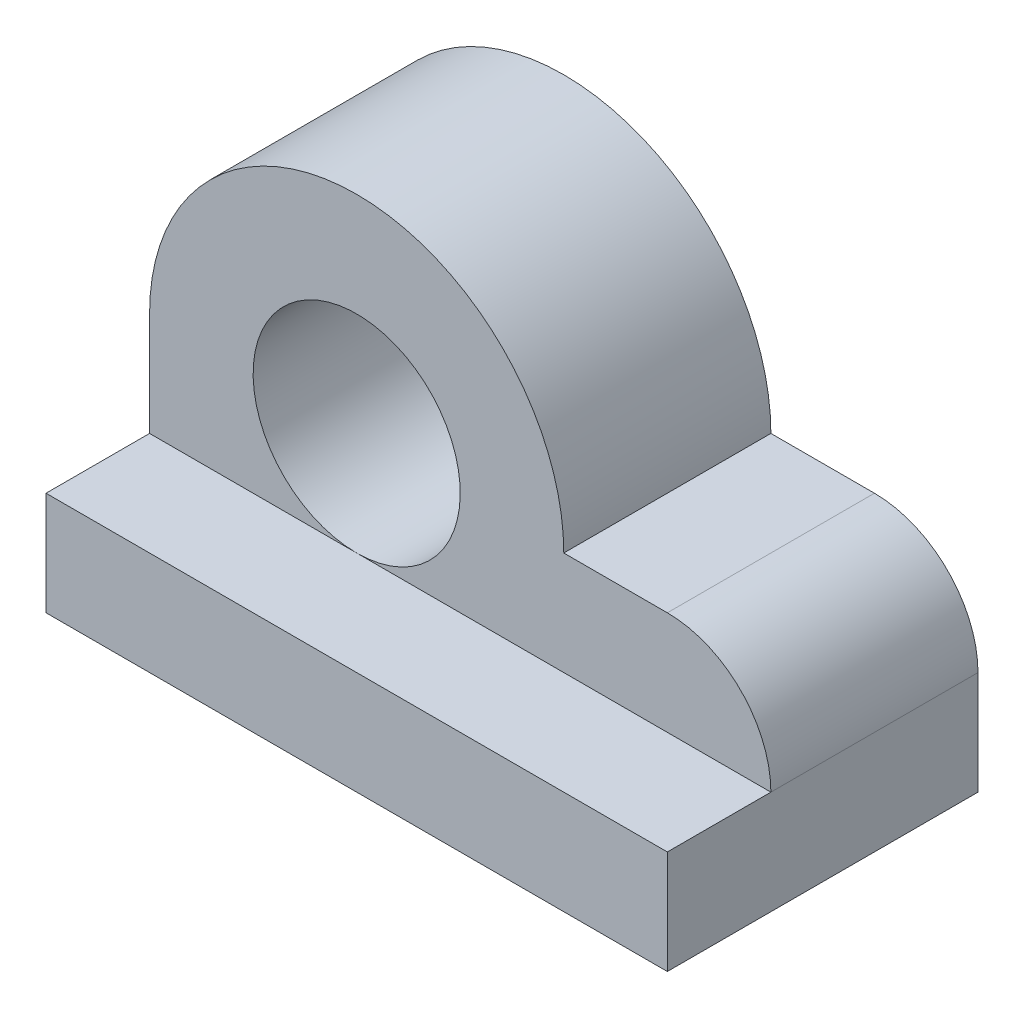
SolidWorks part; units mm, degrees
ref_plane "前基準面" through (0, 0, 0) normal (0, 0, 1) x (1, 0, 0)
ref_plane "上基準面" through (0, 0, 0) normal (0, 1, 0) x (1, 0, 0)
ref_plane "右基準面" through (0, 0, 0) normal (1, 0, 0) x (0, 0, -1)
sketch "草圖1" plane through (0, 0, 0) normal (0, 0, 1) x (1, 0, 0)
  line L0 (0, 0) -> (0, 15.5547) construction
  line L1 (0, 0) -> (-21.833, 0) construction
  line L2 (-2, 0) -> (-2, -2)
  line L3 (-2, -2) -> (4, -2)
  line L4 (4, -2) -> (4, -1)
  line L5 (3, 0) -> (2, 0)
  line L6 (-2, -1) -> (4, -1)
  circle A0 centre (0, 0) radius 1
  arc A1 (2, 0) -> (-2, 0) centre (0, 0) ccw
  arc A2 (4, -1) -> (3, 0) centre (3, -1) ccw
  dimension "D1" = 2
  dimension "D2" = 4
  dimension "D5" = 1
  dimension "D3" = 2
  dimension "D4" = 6
  dimension "D6" = 1
extrude "填料-伸長1" add sketch "草圖1" along normal blind 2 contours L6 A2 L5 A1 L2 A0 | L6 L2 L3 L4 region at (0, 1.9329, 0) region at (1, -1.5, 0)
extrude "填料-伸長2" add sketch "草圖1<3>" along normal blind 3 contours L6 L2 L3 L4 region at (1, -1.5, 0)
sketch "草圖1<3>" plane through (0, 0, 0) normal (0, 0, 1) x (1, 0, 0) same geometry as "草圖1"
